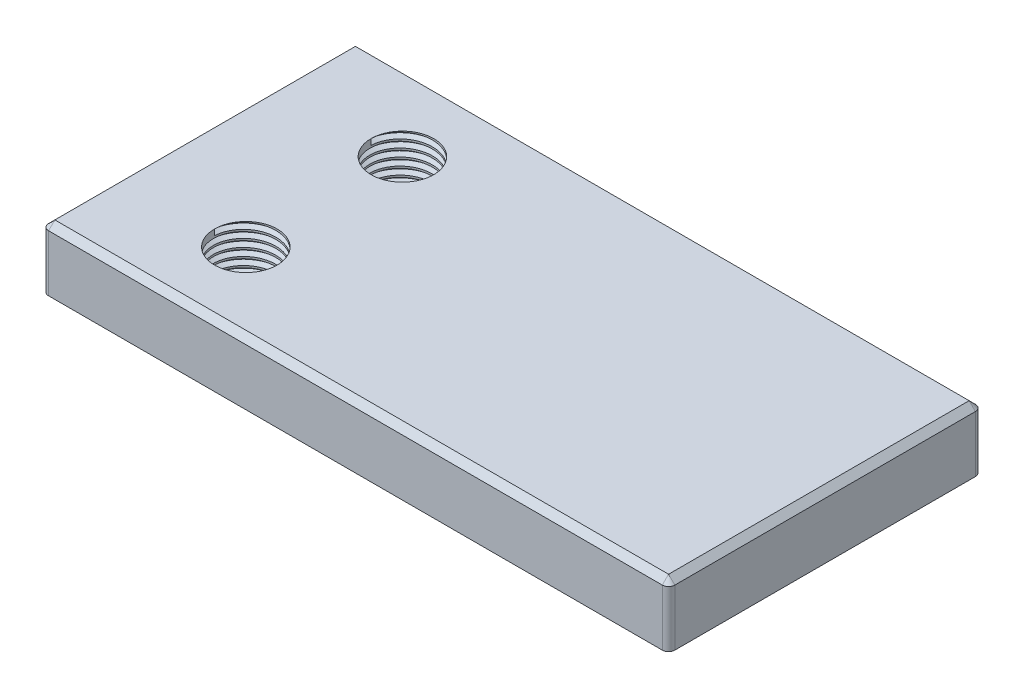
SolidWorks part; units mm, degrees
ref_plane "Front Plane" through (0, 0, 0) normal (0, 0, 1) x (1, 0, 0)
ref_plane "Top Plane" through (0, 0, 0) normal (0, 1, 0) x (1, 0, 0)
ref_plane "Right Plane" through (0, 0, 0) normal (1, 0, 0) x (0, 0, -1)
sketch "Sketch2" plane through (0, 0, 0) normal (0, 1, 0) x (1, 0, 0)
  line L0 (-50, 24) -> (-50, -24)
  line L1 (-49, -25) -> (49, -25)
  line L2 (50, -24) -> (50, 24)
  line L3 (49, 25) -> (-49, 25)
  line L4 (-50, 0) -> (50, 0) construction
  arc A4 (-50, -24) -> (-49, -25) centre (-49, -24) ccw
  arc A5 (49, -25) -> (50, -24) centre (49, -24) ccw
  arc A6 (50, 24) -> (49, 25) centre (49, 24) ccw
  arc A7 (-50, 24) -> (-49, 25) centre (-49, 24) cw
  circle A8 centre (-30, 12.5) radius 5
  circle A9 centre (-30, -12.5) radius 5
  point P3 (0, 25)
  point P5 (-50, 0)
  point P19 (-50, -25)
  point P22 (50, -25)
  point P25 (50, 25)
  dimension "D7" = 1
  dimension "D8" = 10
  dimension "D1" = 50
  dimension "D2" = 100
  dimension "D5" = 20
extrude "Boss-Extrude1" add sketch "Sketch2" along normal mid plane 10
chamfer "Chamfer1" distance 1 angle 45 8 edges at (0, 5, -25) (-49.7071, 5, -24.7071) (49.7071, 5, -24.7071) (-50, 5, 0) (50, 5, 0) (-49.7071, 5, 24.7071) (49.7071, 5, 24.7071) (0, 5, 25)
thread "Thread1" pitch 1.25 method cut profile "Thread Profile2" start angle 0, offset 0, length 10, pitch 1.25, diameter 10
ref_plane "Plane2" through (-35, 5, -12.5) normal (0, 0, 1) x (-1, 0, 0)
sketch "Thread Profile2" plane through (-35, 5, -12.5) normal (0, 0, 1) x (-1, 0, 0)
  line L0 (0, 0) -> (0, 1.25) construction
  line L1 (0, 0) -> (0.6766, 0.3906)
  line L2 (0.6766, 0.3906) -> (0.6766, 0.5469)
  line L3 (0.6766, 0.5469) -> (0, 0.9375)
  line L4 (0.6766, 0.4687) -> (0, 0.4687) construction
  line L11 (0, 0) -> (0, 0.9375)
  point P2 (0, 0)
  dimension "Pitch" = 1.25
  dimension "Profile_Angle" = 60
  dimension "Profile_Land" = 0.1562
  dimension "Profile_Height" = 0.6766
thread "Thread2" pitch 1.25 method cut profile "Thread Profile3" start angle 0, offset 0, length 10, pitch 1.25, diameter 10
ref_plane "Plane3" through (-35, 5, 12.5) normal (0, 0, 1) x (-1, 0, 0)
sketch "Thread Profile3" plane through (-35, 5, 12.5) normal (0, 0, 1) x (-1, 0, 0)
  line L0 (0, 0) -> (0, 1.25) construction
  line L1 (0, 0) -> (0.6766, 0.3906)
  line L2 (0.6766, 0.3906) -> (0.6766, 0.5469)
  line L3 (0.6766, 0.5469) -> (0, 0.9375)
  line L4 (0.6766, 0.4687) -> (0, 0.4687) construction
  line L11 (0, 0) -> (0, 0.9375)
  point P2 (0, 0)
  dimension "Pitch" = 1.25
  dimension "Profile_Angle" = 60
  dimension "Profile_Land" = 0.1562
  dimension "Profile_Height" = 0.6766
